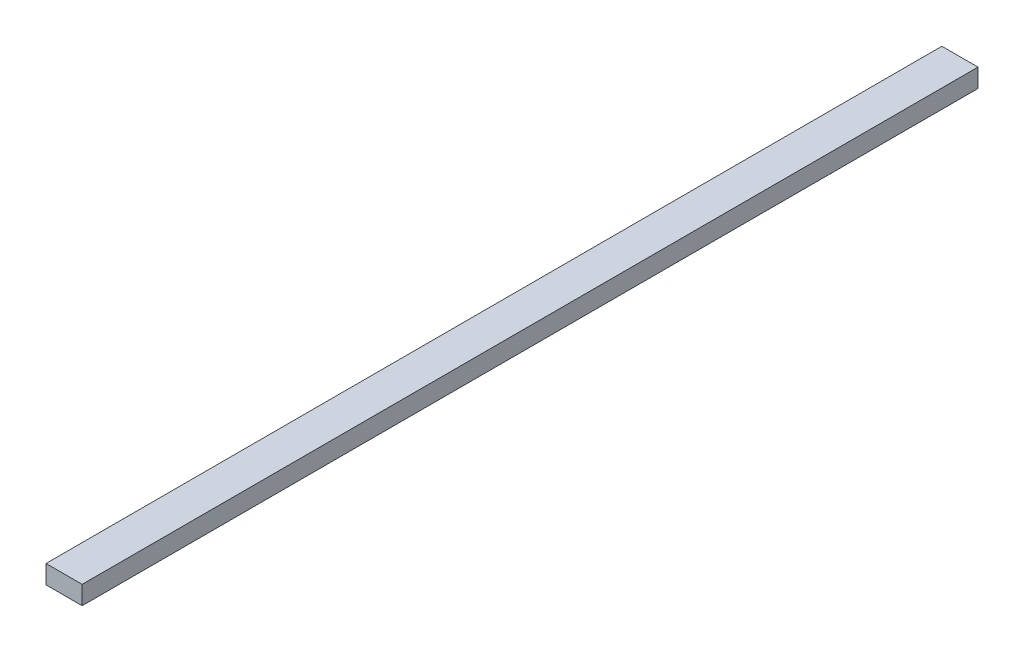
SolidWorks part; units mm, degrees
ref_plane "Front Plane" through (0, 0, 0) normal (0, 0, 1) x (1, 0, 0)
ref_plane "Top Plane" through (0, 0, 0) normal (0, 1, 0) x (1, 0, 0)
ref_plane "Right Plane" through (0, 0, 0) normal (1, 0, 0) x (0, 0, -1)
sketch "Sketch1" plane through (0, 0, 0) normal (0, 0, 1) x (1, 0, 0)
  line L1 (-26.0809, 10.1006) -> (11.9191, 10.1006)
  line L2 (-26.0809, 10.1006) -> (-26.0809, -9.3994)
  line L3 (-26.0809, -9.3994) -> (11.9191, -9.3994)
  line L4 (11.9191, 10.1006) -> (11.9191, -9.3994)
  dimension "D1" = 19.5
  dimension "D2" = 38
extrude "Boss-Extrude1" add sketch "Sketch1" along normal blind 942
